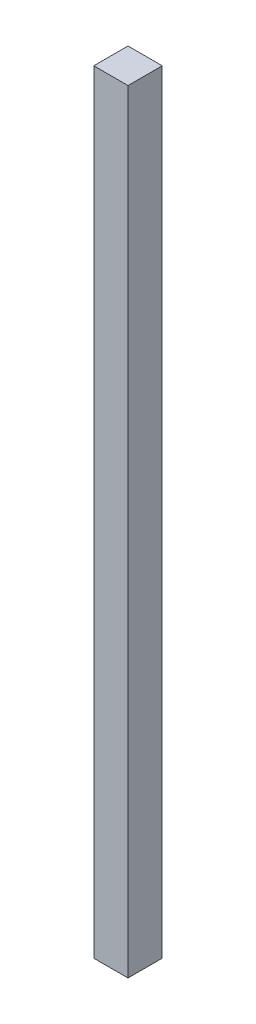
SolidWorks part; units mm, degrees
ref_plane "Front Plane" through (0, 0, 0) normal (0, 0, 1) x (1, 0, 0)
ref_plane "Top Plane" through (0, 0, 0) normal (0, 1, 0) x (1, 0, 0)
ref_plane "Right Plane" through (0, 0, 0) normal (1, 0, 0) x (0, 0, -1)
sketch "Sketch1" plane through (0, 0, 0) normal (0, 1, 0) x (1, 0, 0)
  line L1 (0, 0) -> (25.4, 0)
  line L2 (0, 0) -> (0, 25.4)
  line L3 (0, 25.4) -> (25.4, 25.4)
  line L4 (25.4, 0) -> (25.4, 25.4)
  dimension "D1" = 25.4
  dimension "D2" = 25.4
extrude "Boss-Extrude1" add sketch "Sketch1" along normal blind 609.6
sketch "Sketch3" plane through (0, 0, -25.4) normal (0, 0, -1) x (-1, 0, 0)
  line L0 (0, 609.6) -> (0, 0) construction
  line L1 (0, 466.3042) -> (-25.4, 466.3042)
  line L2 (0, 466.3042) -> (0, 609.6)
  line L3 (0, 609.6) -> (-25.4, 609.6)
  line L4 (-25.4, 466.3042) -> (-25.4, 609.6)
  line L6 (-25.4, 466.3042) -> (0, 466.3042) construction
extrude "Cut-Extrude1" [suppressed] cut sketch "Sketch3" against normal up to surface (25.4 mm away) up to face at (12.7, 304.8, 0)
sketch "Sketch4" [suppressed] plane through (0, 0, 0) normal (0, 0, 1) x (1, 0, 0)
  line L0 (0, 609.6) -> (0, 0) construction
  line L1 (0, 276.4933) -> (25.4, 276.4933)
  line L2 (0, 276.4933) -> (0, 609.6)
  line L3 (0, 609.6) -> (25.4, 609.6)
  line L4 (25.4, 276.4933) -> (25.4, 609.6)
  line L6 (0, 276.4933) -> (25.4, 276.4933) construction
extrude "Cut-Extrude2" [suppressed] cut sketch "Sketch4" against normal up to surface (430.6021 mm away) up to face at (12.7, 304.8, -25.4)
sketch "Sketch5" plane through (0, 0, -25.4) normal (0, 0, -1) x (-1, 0, 0)
  line L0 (0, 609.6) -> (0, 0) construction
  line L1 (0, 573.3313) -> (-25.4, 573.3313)
  line L2 (0, 573.3313) -> (0, 609.6)
  line L3 (0, 609.6) -> (-25.4, 609.6)
  line L4 (-25.4, 573.3313) -> (-25.4, 609.6)
  line L6 (-25.4, 573.3313) -> (0, 573.3313) construction
extrude "Cut-Extrude3" cut sketch "Sketch5" against normal up to surface (25.4 mm away) up to face at (12.7, 304.8, 0)
sketch "Sketch6" [suppressed] plane through (0, 0, -25.4) normal (0, 0, -1) x (-1, 0, 0)
  line L0 (0, 609.6) -> (0, 0) construction
  line L1 (0, 553.696) -> (-25.4, 553.696)
  line L2 (0, 553.696) -> (0, 609.6)
  line L3 (0, 609.6) -> (-25.4, 609.6)
  line L4 (-25.4, 553.696) -> (-25.4, 609.6)
  line L6 (-25.4, 553.696) -> (0, 553.696) construction
extrude "Cut-Extrude4" [suppressed] cut sketch "Sketch6" against normal up to surface (25.4 mm away) up to face at (12.7, 286.6656, 0)
sketch "Sketch7" [suppressed] plane through (0, 0, 0) normal (0, 0, 1) x (1, 0, 0)
  line L0 (25.4, 609.6) -> (25.4, 0) construction
  line L1 (25.4, 422.1079) -> (0, 422.1079)
  line L2 (25.4, 422.1079) -> (25.4, 609.6)
  line L3 (25.4, 609.6) -> (0, 609.6)
  line L4 (0, 422.1079) -> (0, 609.6)
  line L8 (0, 422.1079) -> (25.4, 422.1079) construction
extrude "Cut-Extrude5" [suppressed] cut sketch "Sketch7" against normal up to surface (25.4 mm away) up to face at (12.7, 286.6656, -25.4)
sketch "Sketch8" [suppressed] plane through (0, 0, -25.4) normal (0, 0, -1) x (-1, 0, 0)
  line L0 (0, 609.6) -> (0, 0) construction
  line L1 (0, 319.3022) -> (-25.4, 319.3022)
  line L2 (0, 319.3022) -> (0, 609.6)
  line L3 (0, 609.6) -> (-25.4, 609.6)
  line L4 (-25.4, 319.3022) -> (-25.4, 609.6)
  line L6 (-25.4, 319.3022) -> (0, 319.3022) construction
extrude "Cut-Extrude6" [suppressed] cut sketch "Sketch8" against normal up to surface (25.4 mm away) up to face at (12.7, 286.6656, 0)
sketch "Sketch9" [suppressed] plane through (0, 0, 0) normal (0, 0, 1) x (1, 0, 0)
  line L0 (0, 609.6) -> (0, 0) construction
  line L1 (0, 329.8783) -> (25.4, 329.8783)
  line L2 (0, 329.8783) -> (0, 609.6)
  line L3 (0, 609.6) -> (25.4, 609.6)
  line L4 (25.4, 329.8783) -> (25.4, 609.6)
  line L6 (0, 329.8783) -> (25.4, 329.8783) construction
extrude "Cut-Extrude7" [suppressed] cut sketch "Sketch9" against normal up to surface (25.4 mm away) up to face at (12.7, 286.6656, -25.4)
